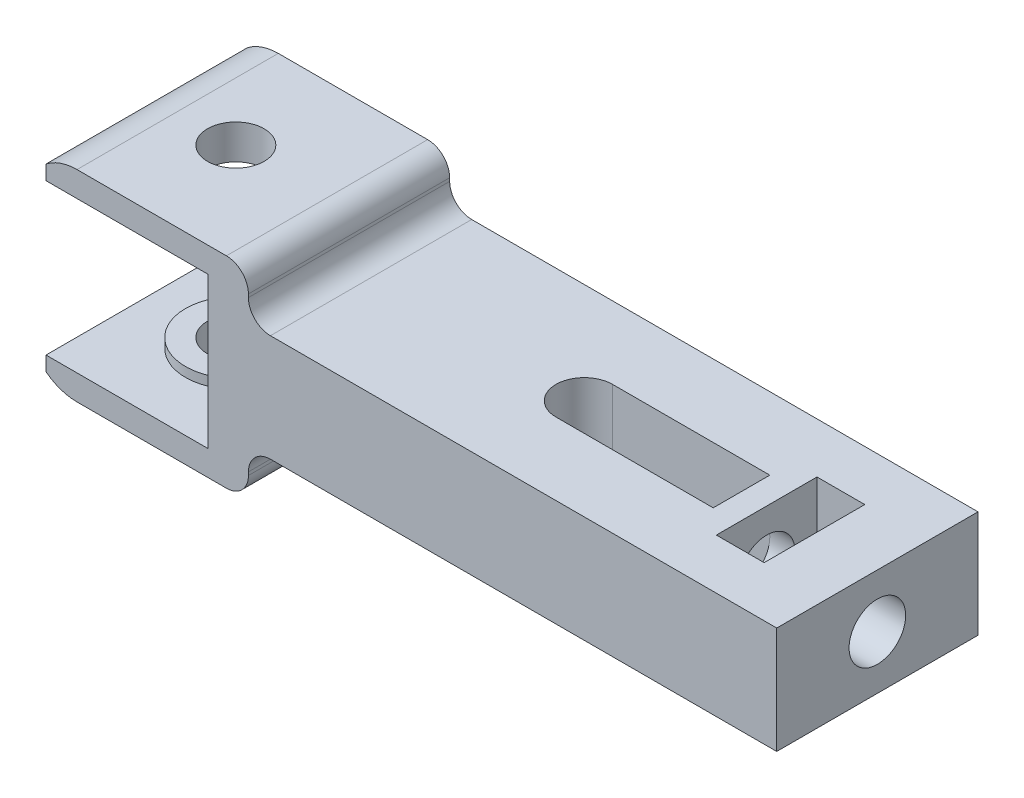
SolidWorks part; units mm, degrees
ref_plane "Front Plane" through (0, 0, 0) normal (0, 0, 1) x (1, 0, 0)
ref_plane "Top Plane" through (0, 0, 0) normal (0, 1, 0) x (1, 0, 0)
ref_plane "Right Plane" through (0, 0, 0) normal (1, 0, 0) x (0, 0, -1)
sketch "Sketch1" plane through (0, 0, 0) normal (0, 0, 1) x (1, 0, 0)
  line L0 (0, 0) -> (-42, 0)
  line L1 (-42, 0) -> (-42, 3.75)
  line L2 (-42, 3.75) -> (-59.5, 3.75)
  line L3 (-59.5, 3.75) -> (-59.5, 0.75)
  line L4 (-59.5, 0.75) -> (-45.5, 0.75)
  line L5 (-45.5, 0.75) -> (-45.5, -9.25)
  line L6 (0, 0) -> (0, -8.5)
  line L7 (0, -4.25) -> (-45.5, -4.25) construction
  line L8 (-59.5, -9.25) -> (-45.5, -9.25)
  line L9 (-59.5, -12.25) -> (-59.5, -9.25)
  line L10 (-42, -12.25) -> (-59.5, -12.25)
  line L11 (-42, -8.5) -> (-42, -12.25)
  line L12 (0, -8.5) -> (-42, -8.5)
  dimension "D1" = 59.5
  dimension "D2" = 14
  dimension "D3" = 4.25
  dimension "D4" = 5
  dimension "D5" = 3
  dimension "D6" = 17.5
extrude "Boss-Extrude1" add sketch "Sketch1" along normal blind 16
sketch "Sketch2" plane through (0, 0, 0) normal (0, 1, 0) x (1, 0, 0)
  line L0 (0, -8) -> (-42, -8) construction
  line L1 (0, -16) -> (0, 0) construction
  line L2 (-42, -16) -> (-42, 0) construction
  line L4 (-8.8, -4) -> (-5, -4)
  line L5 (-8.8, -4) -> (-8.8, -12)
  line L6 (-8.8, -12) -> (-5, -12)
  line L7 (-5, -4) -> (-5, -12)
  line L8 (-8.8, -4) -> (-5, -12) construction
  line L9 (-8.8, -12) -> (-5, -4) construction
  line L10 (-23.3, -10.25) -> (-10.8, -10.25)
  line L12 (-23.3, -5.75) -> (-10.8, -5.75)
  line L13 (-10.8, -10.25) -> (-10.8, -5.75)
  line L14 (-23.3, -10.25) -> (-10.8, -5.75) construction
  line L15 (-23.3, -5.75) -> (-10.8, -10.25) construction
  arc A0 (-23.3, -5.75) -> (-23.3, -10.25) centre (-23.3, -8) ccw
  point P6 (-6.9, -8)
  point P11 (-17.05, -8)
  dimension "D7" = 2.25
  dimension "D1" = 8
  dimension "D2" = 3.8
  dimension "D3" = 5
  dimension "D4" = 2
  dimension "D5" = 4.5
  dimension "D6" = 12.5
extrude "Cut-Extrude1" cut sketch "Sketch2" against normal through all
sketch "Sketch3" plane through (0, 0, 0) normal (1, 0, 0) x (0, 0, -1)
  line L0 (-8, 0) -> (-8, -8.5) construction
  line L1 (-16, 0) -> (0, 0) construction
  line L2 (-16, -8.5) -> (0, -8.5) construction
  circle A0 centre (-8, -4.25) radius 2.25
  dimension "D1" = 4.5
extrude "Cut-Extrude2" cut sketch "Sketch3" against normal up to surface (10.8 mm away) up to face at (-10.8, -4.25, 8)
fillet "Fillet1" radius 1.75 4 edges at (-42, -8.5, 8) (-42, 3.75, 8) (-42, 0, 8) (-42, -12.25, 8)
sketch "Sketch4" plane through (0, -9.25, 0) normal (0, 1, 0) x (1, 0, 0)
  line L0 (-59.5, -8) -> (-43.75, -8) construction
  line L1 (-59.5, -16) -> (-59.5, 0) construction
  line L2 (-43.75, 0) -> (-43.75, -16) construction
  circle A0 centre (-51.625, -8) radius 9.25
  dimension "D1" = 18.5
extrude "Cut-Extrude3" cut sketch "Sketch4" along normal up to surface (10 mm away) up to face at (-52.5, 0.75, 8)
sketch "Sketch5" plane through (0, 3.75, 0) normal (0, 1, 0) x (1, 0, 0)
  line L0 (-59.5, -8) -> (-43.75, -8) construction
  line L1 (-59.5, -16) -> (-59.5, 0) construction
  line L2 (-43.75, -16) -> (-43.75, 0) construction
  circle A0 centre (-51, -8) radius 2.25
  dimension "D1" = 4.5
  dimension "D2" = 8.5
extrude "Cut-Extrude4" cut sketch "Sketch5" against normal through all
fillet "Fillet2" radius 4 2 edges at (-59.5, -12.25, 8) (-59.5, 3.75, 8)
sketch "Sketch6" plane through (0, -9.25, 0) normal (0, 1, 0) x (1, 0, 0)
  line L0 (-51.625, 1.25) -> (-59.5, 1.25)
  line L1 (-59.5, -16) -> (-59.5, 0) construction
  line L2 (-51.625, -17.25) -> (-59.5, -17.25)
  line L3 (-59.5, -17.25) -> (-59.5, 1.25)
  arc A0 (-51.625, -17.25) -> (-51.625, 1.25) centre (-51.625, -8) ccw
  arc A1 (-45.5, -14.9316) -> (-45.5, -1.0684) centre (-51.625, -8) ccw construction
  point P1 (0, 0)
  point P9 (0, 0)
extrude "Cut-Extrude5" cut sketch "Sketch6" against normal blind 1
sketch "Sketch7" plane through (0, -10.25, 0) normal (0, 1, 0) x (1, 0, 0)
  circle A0 centre (-51, -8) radius 4
  circle A1 centre (-51, -8) radius 2.25
  circle A2 centre (-51, -8) radius 2.25 construction
  dimension "D1" = 8
extrude "Boss-Extrude2" add sketch "Sketch7" along normal blind 0.75
ref_plane "Plane1" through (0, -4.25, 0) normal (0, 1, 0) x (1, 0, 0)
mirror "Mirror1" about plane through (0, -4.25, 0) normal (0, 1, 0) of "Boss-Extrude2", "Cut-Extrude5"
sketch "Sketch8" plane through (0, 0, 16) normal (0, 0, 1) x (1, 0, 0)
  line L0 (0, -4.25) -> (-60.0911, -4.25) construction
  line L1 (0, -8.5) -> (0, 0) construction
  line L2 (8.8, -4.25) -> (-8.8, -4.25) construction
  line L3 (-43.75, 3.75) -> (-55.627, 3.75) construction
  line L4 (-62.0911, -12.25) -> (-58.0911, -12.25)
  line L5 (-62.0911, -12.25) -> (-62.0911, 3.75)
  line L6 (-62.0911, 3.75) -> (-58.0911, 3.75)
  line L7 (-58.0911, -12.25) -> (-58.0911, 3.75)
  line L8 (-62.0911, -12.25) -> (-58.0911, 3.75) construction
  line L9 (-62.0911, 3.75) -> (-58.0911, -12.25) construction
  dimension "D1" = 1
  dimension "D2" = 2
extrude "Cut-Extrude6" cut sketch "Sketch8" against normal through all
sketch "Sketch9" plane through (0, 0, 16) normal (0, 0, 1) x (1, 0, 0)
  line L0 (-58.0911, -10.25) -> (-46.9815, -10.25) construction
  line L1 (-46.9815, 1.75) -> (-45.2315, 1.75)
  line L2 (-46.9815, 1.75) -> (-46.9815, -10.25)
  line L3 (-46.9815, -10.25) -> (-45.2315, -10.25)
  line L4 (-45.2315, 1.75) -> (-45.2315, -10.25)
  dimension "D1" = 1.75
extrude "Cut-Extrude7" cut sketch "Sketch9" against normal through all
equation "\"X-ROD-SPACING\"=45"
equation "\"Y-ROD-SPACING\"=75"
equation "\"Z-ROD-SPACING\"=17.5"
equation "\"Y-BED-OFFSET\"=2"
equation "\"Y-BED-ROD-INSET\"=3.5"
equation "\"T-SLOT-NUT-FILLET-RADIUS\"=0.5"
equation "\"T-SLOT-SCREW-SHAFT-RADIUS\"=1.55"
equation "\"T-SLOT-SCREW-SHAFT-CUTOUT-LENGTH\"=11"
equation "\"T-SLOT-NUT-DEPTH\"=3.5"
equation "\"T-SLOT-NUT-WIDTH\"=2.85"
equation "\"T-SLOT-NUT-END-DISTANCE\"=8"
equation "\"ACRYLIC-THICKNESS\"=10"
equation "\"ACRYLIC-TAB-CUTOUT-SIZE\"=\"ACRYLIC-THICKNESS\"+\"ACRYLIC-TAB-TOLERANCE\"*2"
equation "\"ACRYLIC-TAB-WIDTH\"=\"ACRYLIC-THICKNESS\""
equation "\"ACRYLIC-M3-HOLE\"=2.9"
equation "\"SMOOTHROD-CAP-SCREW-DISTANCE\"=20"
equation "\"FRAME-WIDTH-INNER\"=370"
equation "\"NEMA17-HOLE-SPACING\"=31"
equation "\"NEMA17-CENTRAL-CUTOUT\"=22.5"
equation "\"Z-BRACKET-REACH\"=57"
equation "\"TOP-BRACKET-SPACING\"=40"
equation "\"SMOOTHROD-X-LENGTH\"=350"
equation "\"SMOOTHROD-Y-LENGTH\"=350"
equation "\"SMOOTHROD-Z-LENGTH\"=350"
equation "\"SMOOTHROD-TIGHTENING-HEADROOM\"=.25"
equation "\"LEADSCREW-Z-LENGTH\"=300"
equation "\"SCREW-HEAD-RADIUS\"=6"
equation "\"PRINTED-X-SMOOTHROD-DIAMETER\"=8.8"
equation "\"PRINTED-X-SMOOTHROD-CUTOUT\"=10"
equation "\"PRINTED-X-BASE-HEIGHT\"=10"
equation "\"PRINTED-LM8UU-CUTOUT-SIZE\"=15.5"
equation "\"PRINTED-LM8UU-CUTOUT-LENGTH\"=24.5"
equation "\"PRINTED-X-IDLER-HEIGHT\"=16"
equation "\"D1@Boss-Extrude1\"=\"PRINTED-X-IDLER-HEIGHT\""
